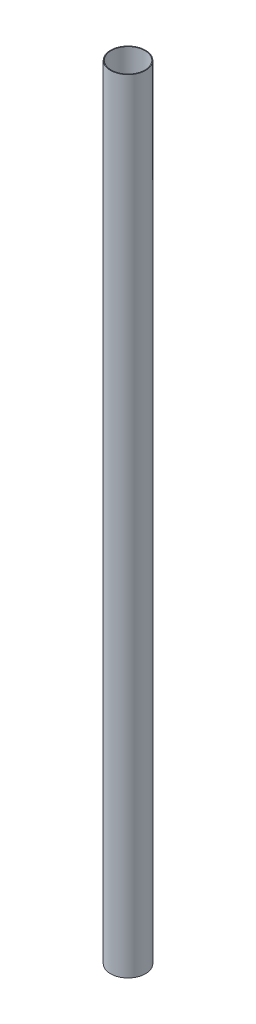
SolidWorks part; units mm, degrees
material "Wildman Fiberglass"
ref_plane "Front Plane" through (0, 0, 0) normal (0, 0, 1) x (1, 0, 0)
ref_plane "Top Plane" through (0, 0, 0) normal (0, 1, 0) x (1, 0, 0)
ref_plane "Right Plane" through (0, 0, 0) normal (1, 0, 0) x (0, 0, -1)
sketch "Sketch1" plane through (0, 0, 0) normal (0, 1, 0) x (1, 0, 0)
  circle A0 centre (0, 0) radius 27.3304
  circle A1 centre (0, 0) radius 28.4734
  dimension "D1" = 56.9468
  dimension "D2" = 54.6608
extrude "Boss-Extrude1" add sketch "Sketch1" along normal blind 1270
equation "\"Length\"= 50"
equation "\"D1@Boss-Extrude1\"=\"Length\""
